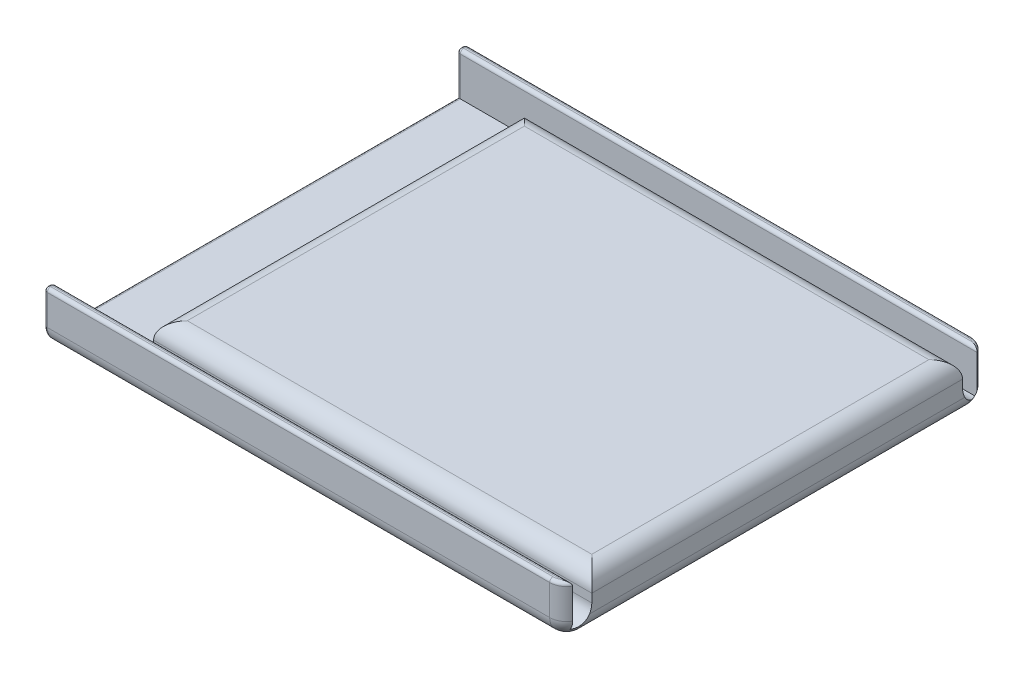
SolidWorks part; units mm, degrees
ref_plane "前视基准面" through (0, 0, 0) normal (0, 0, 1) x (1, 0, 0)
ref_plane "上视基准面" through (0, 0, 0) normal (0, 1, 0) x (1, 0, 0)
ref_plane "右视基准面" through (0, 0, 0) normal (1, 0, 0) x (0, 0, -1)
sketch "草图2" plane through (0, 0, 0) normal (0, 1, 0) x (1, 0, 0)
  line L1 (-15.5, 12.5) -> (15.5, 12.5)
  line L2 (-15.5, 12.5) -> (-15.5, -12.5)
  line L3 (-15.5, -12.5) -> (15.5, -12.5)
  line L4 (15.5, 12.5) -> (15.5, -12.5)
  line L5 (-15.5, 12.5) -> (15.5, -12.5) construction
  line L6 (-15.5, -12.5) -> (15.5, 12.5) construction
  point P0 (0, 0)
  dimension "D1" = 31
  dimension "D2" = 25
extrude "凸台-拉伸1" add sketch "草图2" along normal blind 3
sketch "草图3" plane through (0, 3, 0) normal (0, 1, 0) x (1, 0, 0)
  line L0 (-15.5, 12.5) -> (-15.5, -12.5) construction
  line L1 (-15.5, 12) -> (15.5, 12)
  line L2 (-15.5, 12) -> (-15.5, 11)
  line L3 (-15.5, 11) -> (15.5, 11)
  line L4 (15.5, 12) -> (15.5, 11)
  line L5 (15.5, -12.5) -> (15.5, 12.5) construction
  line L6 (15.5, 12.5) -> (-15.5, 12.5) construction
  line L7 (-15.5, 0) -> (15.5, 0) construction
  line L8 (15.5, -12) -> (15.5, -11)
  line L9 (-15.5, -11) -> (15.5, -11)
  line L10 (-15.5, -12) -> (-15.5, -11)
  line L11 (-15.5, -12) -> (15.5, -12)
  dimension "D1" = 1
  dimension "D2" = 0.5
extrude "切除-拉伸1" cut sketch "草图3" against normal blind 2.5
sketch "草图4" plane through (0, 3, 0) normal (0, 1, 0) x (1, 0, 0)
  line L0 (15.5, -11) -> (-15.5, -11) construction
  line L1 (-15.5, 11) -> (-10.5, 11)
  line L2 (-15.5, 11) -> (-15.5, -11)
  line L3 (-15.5, -11) -> (-10.5, -11)
  line L4 (-10.5, 11) -> (-10.5, -11)
  dimension "D1" = 5
extrude "切除-拉伸2" cut sketch "草图4" against normal blind 2.5
fillet "圆角11" radius 1 1 edges at (0, 0, 12.5)
fillet "圆角12" radius 1 1 edges at (0, 0, -12.5)
fillet "圆角13" radius 1 3 edges at (15.5, 2, 12.5) (15.5, 2, -12.5) (15.5, 0, 0)
fillet "圆角18" radius 1 4 edges at (2.5, 3, -11) (15.5, 3, 0) (2.5, 3, 11) (-10.5, 3, 0)
fillet "圆角19" radius 1 1 edges at (-10.5, 0.5, 0)
fillet "圆角20" radius 1 1 edges at (1.933, 0.5, -11)
fillet "圆角21" radius 1 1 edges at (1.933, 0.5, 11)
fillet "圆角22" radius 0.2 4 edges at (-15.5, 3, 12.25) (-0.067, 3, 12) (15, 3, 12.366) (-0.5, 3, 12.5)
fillet "圆角23" radius 0.2 4 edges at (-15.5, 3, -12.25) (-0.5, 3, -12.5) (15, 3, -12.366) (-0.067, 3, -12)
fillet "圆角24" radius 0.2 12 edges at (-15.4414, 2.9414, 12.0586) (-15.4414, 2.9414, -12.4414) (-15.4414, 2.9414, 12.4414) (-15.4414, 2.9414, -12.0586) (-15.5, 0.5, 0) (-15.5, 1.65, 12) (-15.5, 1.9, 12.5) (-15.5, 0.2929, 12.2071) (-15.5, 0, 0) (-15.5, 0.2929, -12.2071) (-15.5, 1.9, -12.5) (-15.5, 1.65, -12)
